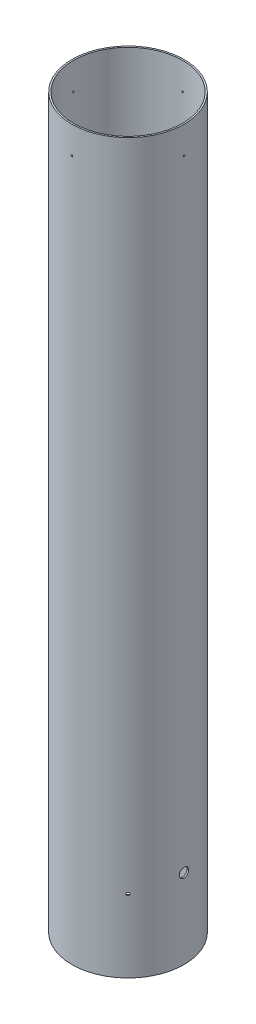
SolidWorks part; units mm, degrees
material "A-Glass Fiber"
ref_plane "Front Plane" through (0, 0, 0) normal (0, 0, 1) x (1, 0, 0)
ref_plane "Top Plane" through (0, 0, 0) normal (0, 1, 0) x (1, 0, 0)
ref_plane "Right Plane" through (0, 0, 0) normal (1, 0, 0) x (0, 0, -1)
sketch "Sketch1" plane through (0, 0, 0) normal (0, 1, 0) x (1, 0, 0)
  circle A0 centre (0, 0) radius 76.1746
  circle A1 centre (0, 0) radius 78.359
  dimension "D1" = 156.718
  dimension "D2" = 152.3492
extrude "Boss-Extrude1" add sketch "Sketch1" along normal blind 1016
ref_axis "Axis1" through (0, 1016, 0) along (0, -1, 0)
sketch "Sketch2" plane through (0, 0, 0) normal (1, 0, 0) x (0, 0, -1)
  line L0 (78.359, 1016) -> (-78.359, 1016) construction
  circle A0 centre (0, 977.9) radius 1.0922
  dimension "D1" = 2.1844
  dimension "D2" = 38.1
extrude "Cut-Extrude1" cut sketch "Sketch2" against normal through all
pattern_circular "CirPattern1" count 4 over 360 about axis through (0, 1016, 0) along (0, 1, 0) of "Cut-Extrude1"
hole_wizard "1/2 Clearance Hole1" positions "Sketch3" profile "Sketch4" hole size "1/2" standard "ANSI Inch"
sketch "Sketch3" plane through (0, 0, 0) normal (1, 0, 0) x (0, 0, -1)
  point P0 (0, 111.125)
  dimension "D1" = 111.125
sketch "Sketch4" plane through (0, 111.125, 0) normal (0, 1, 0) x (0, 0, 1)
  line L0 (0, 0) -> (0, 92.8345)
  line L1 (0, 92.8345) -> (6.5481, 88.9)
  line L2 (6.5481, 88.9) -> (6.5481, 0)
  line L5 (6.5481, 0) -> (0, 0)
  line L10 (0, 92.8345) -> (-6.5481, 88.9) construction
  line L11 (0, -6.35) -> (0, 107.95) construction
  dimension "Hole Dia." = 13.0962
  dimension "Hole Depth" = 88.9
  dimension "Drill Angle" = 118
ref_plane "Forward Body Tube Screw Plane" through (0, 0, 0) normal (0.7071, 0, 0.7071) x (0, -1, 0)
hole_wizard "Ø4.0 (4) Diameter Hole - Forward Body Tube Secure" positions "Sketch5" profile "Sketch6" hole size "Ø4.0" standard "ANSI Metric"
sketch "Sketch5" plane through (0, 0, 0) normal (0.7071, 0, 0.7071) x (0, -1, 0)
  line L0 (0, -78.359) -> (0, 78.359) construction
  line L1 (-1016, 0) -> (0, 0) construction
  point P0 (-101.6, 0)
  dimension "D1" = 101.6
sketch "Sketch6" plane through (0, 101.6, 0) normal (0, 1, 0) x (-0.7071, 0, 0.7071)
  line L0 (0, 0) -> (0, 90.1017)
  line L1 (0, 90.1017) -> (2, 88.9)
  line L2 (2, 88.9) -> (2, 0)
  line L5 (2, 0) -> (0, 0)
  line L10 (0, 90.1017) -> (-2, 88.9) construction
  line L11 (0, -6.35) -> (0, 107.95) construction
  dimension "Hole Dia." = 4
  dimension "Hole Depth" = 88.9
  dimension "Drill Angle" = 118
pattern_circular "CirPattern2" count 4 over 360 about axis through (0, 0, 0) along (0, 1, 0) of "Ø4.0 (4) Diameter Hole - Forward Body Tube Secure"
equation "\"Fwd_Tube_Length\" = 40in"
equation "\"D1@Boss-Extrude1\" = \"Fwd_Tube_Length\""
equation "\"BKHD_Screw_Diam\"= 3.5mm"
equation "\"Fwd_BKHD_From_Top\" = 18in"
equation "\"Bodytube_OD\" = 6.17in"
equation "\"Bodytube_ID\" = 5.998in"
equation "\"D2@Sketch1\"=\"Bodytube_ID\""
equation "\"D1@Sketch1\"=\"Bodytube_OD\""
equation "\"Shear_Screw_Diameter\" = 0.086in"
equation "\"Shear_Screw_Coupler_Location\" = 4.5in"
equation "\"Motor_OD\" = 4in"
equation "\"Mid_Tube_Length\"= 1in"
equation "\"Mid_Coupler_Length\" = 13in"
equation "\"Aft_Section_Length\"= 39in"
equation "\"AB_Coupler_OD_Length\"= 1in"
equation "\"AB_Coupling_Section_Length\"= 0.375in"
equation "\"AB_Coupler_Length\"= \"AB_Coupler_OD_Length\" + \"AB_Coupling_Section_Length\" * 2"
equation "\"Cutout_Angle\" = 80"
equation "\"AB_Paddle_Height\" = 0.375in"
equation "\"AB_Coupler_Num_Screws\"= 4"
equation "\"AB_BKHD_Thickness\" = 0.375in"
equation "\"AB_Mount_From_Bottom\" = 23.175in"
equation "\"Num_Cutouts\" = 3"
equation "\"AB_Coupler_OD\"= 6.17in"
equation "\"AB_Coupler_ID\"= 5.75in"
equation "\"AB_Coupler_Surface_Diameter\"= 5.998in"
equation "\"AB_Coupling_Screw_Diameter\"= 0.15748in"
equation "\"AB_Central_Bushing_Length\" = .4724in"
equation "\"Lead_Screw_Dist\" = 3.4in"
equation "\"Lead_Screw_Diam\" = 0.386in"
equation "\"Lead_Screw_Length\" = (\"Mid_Coupler_Length\" + 2*0.375in + 2*0.5in)"
equation "\"Paddle_Pin_Offset\" = .25in"
equation "\"Paddle_Pin_Radius\" = 2.25in"
equation "\"SS_Paddle_Pin_Radius\" = 2.25*0.66in"
equation "\"Paddle_Gear_OD\" = 3.2in"
equation "\"Drive_Gear_OD\" = 1.7in"
equation "\"Fin_Thickness\"= .118in"
equation "\"Guiderail_Cutout_Diameter\"= 1.5in"
equation "\"DB9_Hole_Dist\" = 25mm"
equation "\"DB9_Relief_Width\" = 0.47in"
equation "\"DB9_Relief_Hole_Offset\" = 0.09in"
equation "\"Airbrakes_Wire_Hole_Dia\" = .25in"
equation "\"Airbrakes_Wire_Hole_Dist\" = 1.1in"
equation "\"Servo_Gear_Offset\" = 0.5in"
equation "\"D1@Sketch2\"=\"Shear_Screw_Diameter\""
equation "\"FWD_Shear_Screw_Dist\" = 1.5in"
equation "\"D2@Sketch2\"=\"FWD_Shear_Screw_Dist\""
